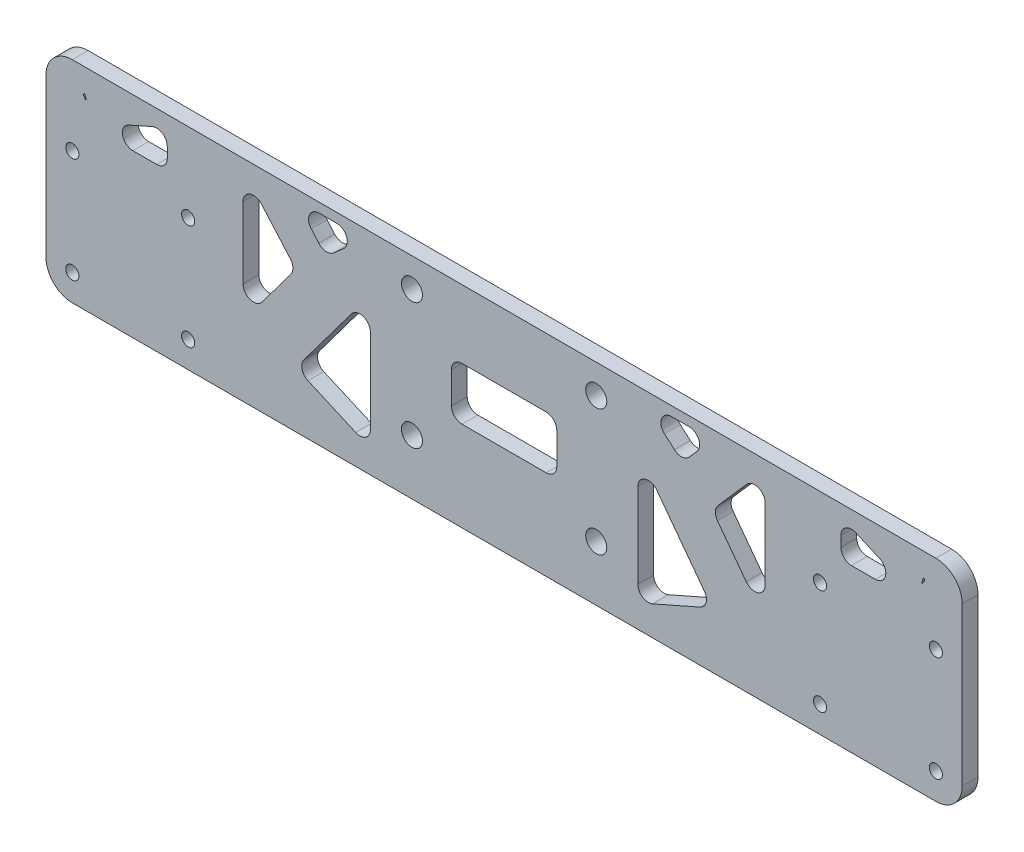
SolidWorks part; units mm, degrees
material "Thornel Mat VMA"
ref_plane "前视基准面" through (0, 0, 0) normal (0, 0, 1) x (1, 0, 0)
ref_plane "上视基准面" through (0, 0, 0) normal (0, 1, 0) x (1, 0, 0)
ref_plane "右视基准面" through (0, 0, 0) normal (1, 0, 0) x (0, 0, -1)
other "Configuration Table"
sketch "草图1" plane through (0, 0, 0) normal (0, 0, 1) x (1, 0, 0)
  line L0 (87, 0) -> (87, -45) construction
  line L1 (0, 0) -> (174, 0)
  line L2 (0, 0) -> (0, -45)
  line L3 (0, -45) -> (174, -45)
  line L4 (174, 0) -> (174, -45)
  line L5 (0, -22.5) -> (174, -22.5) construction
  circle A0 centre (69.5, -10.5) radius 2
  circle A1 centre (104.5, -10.5) radius 2
  circle A2 centre (69.5, -34.5) radius 2
  circle A3 centre (104.5, -34.5) radius 2
  dimension "D3" = 4
  dimension "D4" = 12
  dimension "D5" = 17.5
  dimension "D1" = 174
  dimension "D2" = 45
extrude "凸台-拉伸1" add sketch "草图1" along normal blind 3
sketch "草图2" plane through (0, 0, 3) normal (0, 0, 1) x (1, 0, 0)
  line L0 (87, 0) -> (87, -118.0863) construction
  line L1 (174, 0) -> (0, 0) construction
  line L2 (0, -45) -> (174, -45) construction
  line L4 (16, 4.2756) -> (16, -54.352) construction
  circle A0 centre (147, -20) radius 1.25
  circle A1 centre (147, -40) radius 1.25
  circle A2 centre (27, -40) radius 1.25
  circle A3 centre (27, -20) radius 1.25
  circle A4 centre (5, -20) radius 1.25
  circle A5 centre (5, -40) radius 1.25
  circle A6 centre (169, -40) radius 1.25
  circle A7 centre (169, -20) radius 1.25
  dimension "D1" = 2.5
  dimension "D3" = 5
  dimension "D5" = 11
  dimension "D4" = 164
  dimension "D2" = 2
extrude "切除-拉伸1" cut sketch "草图2" against normal blind 3
sketch "草图3" plane through (0, 0, 3) normal (0, 0, 1) x (1, 0, 0)
  line L0 (6.9646, -8.4465) -> (15.1518, -8.4465)
  line L1 (15.1518, -8.4465) -> (6.9646, -12.0373)
  line L2 (6.9646, -12.0373) -> (6.9646, -8.4465)
  line L3 (6.9646, -14.2202) -> (23.0317, -7.1732)
  line L4 (23.0317, -7.1732) -> (23.0317, -14.2202)
  line L5 (23.0317, -14.2202) -> (6.9646, -14.2202)
  line L6 (37.4157, -6.7984) -> (47.4569, -18.2585)
  line L7 (47.4569, -18.2585) -> (37.4157, -31.6832)
  line L8 (37.4157, -31.6832) -> (37.4157, -6.7984)
  line L9 (47.4569, -6.7984) -> (53.1373, -13.2815)
  line L10 (53.1373, -13.2815) -> (60.5364, -6.7984)
  line L11 (60.5364, -6.7984) -> (47.4569, -6.7984)
  line L12 (47.4569, -34.4118) -> (61.6109, -15.4886)
  line L13 (61.6109, -15.4886) -> (61.6109, -40.633)
  line L14 (61.6109, -40.633) -> (47.4569, -34.4118)
  line L15 (87, 0) -> (87, -71.8481) construction
  line L16 (174, 0) -> (0, 0) construction
  line L17 (112.3891, -40.633) -> (126.5431, -34.4118)
  line L18 (112.3891, -15.4886) -> (112.3891, -40.633)
  line L19 (126.5431, -34.4118) -> (112.3891, -15.4886)
  line L20 (113.4636, -6.7984) -> (126.5431, -6.7984)
  line L21 (120.8627, -13.2815) -> (113.4636, -6.7984)
  line L22 (126.5431, -6.7984) -> (120.8627, -13.2815)
  line L23 (136.5843, -31.6832) -> (136.5843, -6.7984)
  line L24 (126.5431, -18.2585) -> (136.5843, -31.6832)
  line L25 (136.5843, -6.7984) -> (126.5431, -18.2585)
  line L26 (150.9683, -14.2202) -> (167.0354, -14.2202)
  line L27 (150.9683, -7.1732) -> (150.9683, -14.2202)
  line L28 (167.0354, -14.2202) -> (150.9683, -7.1732)
  line L29 (167.0354, -12.0373) -> (167.0354, -8.4465)
  line L30 (158.8482, -8.4465) -> (167.0354, -12.0373)
  line L31 (167.0354, -8.4465) -> (158.8482, -8.4465)
  line L33 (77, -27.9501) -> (97, -27.9501)
  line L34 (77, -27.9501) -> (77, -17.9501)
  line L35 (77, -17.9501) -> (97, -17.9501)
  line L36 (97, -27.9501) -> (97, -17.9501)
  line L37 (77, -27.9501) -> (97, -17.9501) construction
  line L38 (77, -17.9501) -> (97, -27.9501) construction
  point P34 (87, -22.9501)
  dimension "D1" = 10
  dimension "D2" = 20
extrude "切除-拉伸2" cut sketch "草图3" against normal blind 4
fillet "圆角1" radius 2 34 edges at (15.1518, -8.4465, 1.5) (6.9646, -12.0373, 1.5) (6.9646, -8.4465, 1.5) (77, -27.9501, 1.5) (77, -17.9501, 1.5) (97, -17.9501, 1.5) (97, -27.9501, 1.5) (167.0354, -8.4465, 1.5) (167.0354, -12.0373, 1.5) (158.8482, -8.4465, 1.5) (126.5431, -34.4118, 1.5) (112.3891, -40.633, 1.5) (112.3891, -15.4886, 1.5) (126.5431, -6.7984, 1.5) (120.8627, -13.2815, 1.5) (113.4636, -6.7984, 1.5) (136.5843, -6.7984, 1.5) (136.5843, -31.6832, 1.5) (167.0354, -14.2202, 1.5) (150.9683, -14.2202, 1.5) (150.9683, -7.1732, 1.5) (23.0317, -7.1732, 1.5) (23.0317, -14.2202, 1.5) (6.9646, -14.2202, 1.5) (47.4569, -18.2585, 1.5) (37.4157, -31.6832, 1.5) (37.4157, -6.7984, 1.5) (53.1373, -13.2815, 1.5) (47.4569, -6.7984, 1.5) (60.5364, -6.7984, 1.5) (61.6109, -15.4886, 1.5) (61.6109, -40.633, 1.5) (47.4569, -34.4118, 1.5) (126.5431, -18.2585, 1.5)
fillet "圆角2" radius 5 4 edges at (0, 0, 1.5) (174, -45, 1.5) (0, -45, 1.5) (174, 0, 1.5)
sketch "草图4" plane through (0, 0, 3) normal (0, 0, 1) x (1, 0, 0)
  line L0 (174, -40) -> (174, -5) construction
  line L1 (174, -5) -> (80.7642, -5)
  line L2 (174, -5) -> (174, 0)
  line L3 (174, 0) -> (80.7642, 0)
  line L4 (80.7642, -5) -> (80.7642, 0)
  line L5 (169, 0) -> (5, 0) construction
  line L6 (87, 0) -> (87, -81.5728) construction
  line L7 (93.2358, -5) -> (93.2358, 0)
  line L8 (0, 0) -> (93.2358, 0)
  line L9 (0, -5) -> (93.2358, -5)
  line L10 (93.2358, -5) -> (93.2358, 0)
  line L11 (0, 0) -> (93.2358, 0)
  line L12 (0, -5) -> (0, 0)
  line L13 (0, -5) -> (93.2358, -5)
  dimension "D1" = 5
extrude "切除-拉伸3" cut sketch "草图4" against normal blind 4 contours L4 L1 L2 L3 | L12 L9 L7 L8 | L3 L4 L1 L2 region at (133.6179, -2.5, 3) region at (40.3821, -2.5, 3)
fillet "圆角3" radius 5 2 edges at (0, -5, 1.5) (174, -5, 1.5)
